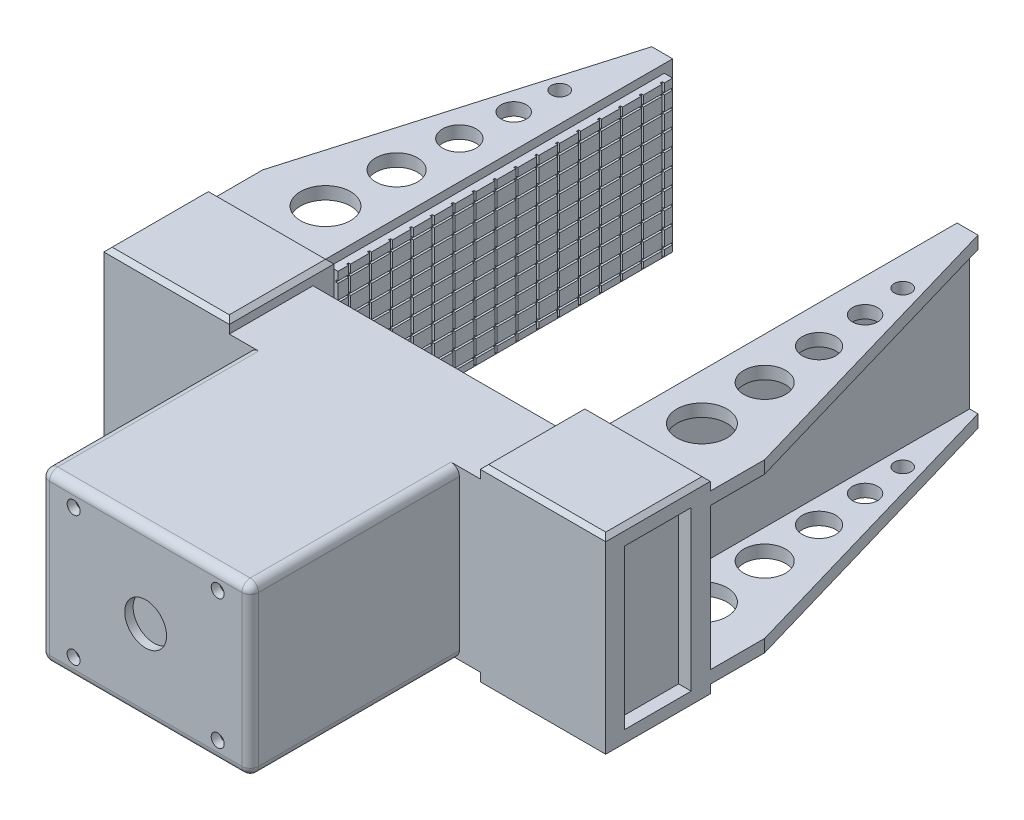
SolidWorks part; units mm, degrees
material "PLA+"
ref_plane "Front Plane" through (0, 0, 0) normal (0, 0, 1) x (1, 0, 0)
ref_plane "Top Plane" through (0, 0, 0) normal (0, 1, 0) x (1, 0, 0)
ref_plane "Right Plane" through (0, 0, 0) normal (1, 0, 0) x (0, 0, -1)
sketch "Sketch1" plane through (0, 0, 0) normal (0, 0, 1) x (1, 0, 0)
  line L1 (-17.2222, -15.5) -> (17.2222, -15.5) construction
  line L2 (-17.2222, -15.5) -> (-17.2222, 15.5) construction
  line L3 (-17.2222, 15.5) -> (17.2222, 15.5) construction
  line L4 (17.2222, -15.5) -> (17.2222, 15.5) construction
  line L5 (-17.2222, -15.5) -> (17.2222, 15.5) construction
  line L6 (-17.2222, 15.5) -> (17.2222, -15.5) construction
  line L7 (-25, -20) -> (25, -20)
  line L8 (-25, -20) -> (-25, 20)
  line L9 (-25, 20) -> (25, 20)
  line L10 (25, -20) -> (25, 20)
  line L11 (-25, -20) -> (25, 20) construction
  line L12 (-25, 20) -> (25, -20) construction
  circle A0 centre (0, 0) radius 5
  circle A1 centre (-17.2222, 15.5) radius 1.55
  circle A2 centre (17.2222, -15.5) radius 1.55
  circle A3 centre (17.2222, 15.5) radius 1.55
  circle A4 centre (-17.2222, -15.5) radius 1.55
  dimension "D1" = 10
  dimension "D3" = 3.1
  dimension "D2" = 15.5
  dimension "D4" = 50
  dimension "D5" = 40
extrude "Boss-Extrude2" add sketch "Sketch1" against normal blind 50 contours L8 L7 L10 L9
sketch "Sketch2" plane through (0, 0, 0) normal (0, 0, 1) x (1, 0, 0)
  circle A5 centre (-17.2222, -15.5) radius 1.55 construction
  circle A6 centre (17.2222, -15.5) radius 1.55 construction
  circle A7 centre (0, 0) radius 5 construction
  circle A8 centre (17.2222, 15.5) radius 1.55 construction
  circle A9 centre (-17.2222, 15.5) radius 1.55 construction
  circle A10 centre (-17.2222, -15.5) radius 1.55
  circle A11 centre (17.2222, -15.5) radius 1.55
  circle A12 centre (0, 0) radius 5
  circle A13 centre (17.2222, 15.5) radius 1.55
  circle A14 centre (-17.2222, 15.5) radius 1.55
extrude "Cut-Extrude1" cut sketch "Sketch2" against normal blind 2
sketch "Sketch3" plane through (0, 0, -50) normal (0, 0, -1) x (-1, 0, 0)
  line L1 (-60, -20) -> (60, -20)
  line L2 (-60, -20) -> (-60, 20)
  line L3 (-60, 20) -> (60, 20)
  line L4 (60, -20) -> (60, 20)
  line L5 (-60, -20) -> (60, 20) construction
  line L6 (-60, 20) -> (60, -20) construction
  point P0 (0, 0)
  dimension "D1" = 120
  dimension "D2" = 40
extrude "Boss-Extrude3" add sketch "Sketch3" along normal blind 20
sketch "Sketch4" plane through (0, 0, -70) normal (0, 0, -1) x (-1, 0, 0)
  line L0 (-60, -20) -> (60, -20) construction
  line L1 (-60, 20) -> (-34, 20)
  line L2 (-60, 20) -> (-60, -20)
  line L3 (-60, -20) -> (-34, -20)
  line L4 (-34, 20) -> (-34, -20)
  dimension "D1" = 26
extrude "Boss-Extrude4" add sketch "Sketch4" along normal blind 90 separate body
shell "Shell1" thickness 3
sketch "Sketch5" plane through (0, 0, 0) normal (0, 1, 0) x (1, 0, 0)
  line L0 (39, 160) -> (60, 88)
  line L1 (60, 70) -> (34, 70) construction
  line L3 (39, 160) -> (34, 160) construction
  line L4 (34, 70) -> (34, 160) construction
  line L5 (39, 160) -> (39, 70) construction
  line L6 (60, 88) -> (60, 70) construction
  line L7 (60, 70) -> (34, 70) construction
  line L8 (34, 70) -> (34, 160) construction
  line L9 (34, 160) -> (39, 160) construction
  line L10 (39, 160) -> (60, 160)
  line L11 (60, 160) -> (60, 88)
  circle A0 centre (41, 140) radius 2
  circle A1 centre (42, 130) radius 3
  circle A2 centre (43, 118) radius 4
  circle A3 centre (45, 88) radius 6
  circle A4 centre (44, 104) radius 5
  dimension "D3" = 4
  dimension "D4" = 6
  dimension "D5" = 8
  dimension "D6" = 12
  dimension "D7" = 10
  dimension "D1" = 5
  dimension "D2" = 18
  dimension "D8" = 10
  dimension "D9" = 12
  dimension "D10" = 14
  dimension "D11" = 16
  dimension "D12" = 20
extrude "Cut-Extrude2" cut sketch "Sketch5" against normal through all both and the other way through all
mirror "Mirror3" about plane through (0, 0, 0) normal (1, 0, 0) of bodies 106
sketch "Sketch7" plane through (34, 0, 0) normal (-1, 0, 0) x (0, 0, 1)
  line L0 (-160, 20) -> (-70, 20) construction
  line L1 (-158, 18) -> (-78, 18)
  line L2 (-158, 18) -> (-158, -18)
  line L3 (-158, -18) -> (-78, -18)
  line L4 (-78, 18) -> (-78, -18)
  line L5 (-160, -20) -> (-160, 20) construction
  line L6 (-160, -20) -> (-70, -20) construction
  dimension "D1" = 2
  dimension "D2" = 2
  dimension "D3" = 80
  dimension "D4" = 2
extrude "Boss-Extrude6" add sketch "Sketch7" along normal blind 2 separate body
sketch "Sketch8" plane through (32, 0, 0) normal (-1, 0, 0) x (0, 0, 1)
  line L0 (-156, 22.9676) -> (-156, -23.6029)
  line L1 (-158, 18) -> (-158, -18) construction
  line L2 (-155.5, 22.9676) -> (-155.5, -23.6029)
  line L3 (-156, 22.9676) -> (-155.5, 22.9676)
  line L4 (-156, -23.6029) -> (-155.5, -23.6029)
  dimension "D1" = 2
  dimension "D2" = 0.5
extrude "Cut-Extrude3" cut sketch "Sketch8" against normal blind 0.5
pattern_linear "LPattern1" count 16 spacing 5 along (0, 0, 1) of "Cut-Extrude3"
sketch "Sketch9" plane through (32, 0, 0) normal (-1, 0, 0) x (0, 0, 1)
  line L0 (-164.1465, 16) -> (-74.0827, 16)
  line L1 (-74.0827, 16) -> (-74.0827, 15.5)
  line L2 (-74.0827, 15.5) -> (-164.1465, 15.5)
  line L3 (-164.1465, 15.5) -> (-164.1465, 16)
  line L4 (-151, 18) -> (-155.5, 18) construction
  dimension "D1" = 0.5
  dimension "D2" = 2
extrude "Cut-Extrude4" cut sketch "Sketch9" against normal blind 0.5
pattern_linear "LPattern2" count 9 spacing 4 along (0, -1, 0) of "Cut-Extrude4"
mirror "Mirror4" about plane through (0, 0, 0) normal (1, 0, 0) of bodies 113
sketch "Sketch10" plane through (60, 0, 0) normal (1, 0, 0) x (0, 0, -1)
  line L0 (70, 20) -> (70, -20) construction
  line L1 (50, 23) -> (75, 23)
  line L2 (50, 23) -> (50, -23)
  line L3 (50, -23) -> (75, -23)
  line L4 (75, 23) -> (75, -23)
  line L5 (70, 20) -> (50, 20) construction
  line L6 (70, -20) -> (50, -20) construction
  point P10 (62.5, -23)
  dimension "D1" = 5
  dimension "D2" = 3
  dimension "D3" = 3
extrude "Boss-Extrude7" add sketch "Sketch10" against normal blind 30
sketch "Sketch11" plane through (60, 0, 0) normal (1, 0, 0) x (0, 0, -1)
  line L1 (54.4268, -19.1464) -> (70.4268, -19.1464)
  line L2 (54.4268, -19.1464) -> (54.4268, 18.8536)
  line L3 (54.4268, 18.8536) -> (70.4268, 18.8536)
  line L4 (70.4268, -19.1464) -> (70.4268, 18.8536)
  line L5 (54.4268, -19.1464) -> (70.4268, 18.8536) construction
  line L6 (54.4268, 18.8536) -> (70.4268, -19.1464) construction
  point P0 (62.4268, -0.1464)
  dimension "D1" = 16
  dimension "D2" = 38
extrude "Cut-Extrude5" cut sketch "Sketch11" against normal blind 3
sketch "Sketch12" plane through (-60, 0, 0) normal (-1, 0, 0) x (0, 0, 1)
  line L0 (-50, -20) -> (-50, -23) construction
  line L1 (-75, 23) -> (-50, 23)
  line L2 (-75, 23) -> (-75, -23)
  line L3 (-75, -23) -> (-50, -23)
  line L4 (-50, 23) -> (-50, -23)
extrude "Boss-Extrude8" add sketch "Sketch12" against normal blind 30
mirror "Mirror11" about plane through (0, 0, 0) normal (1, 0, 0) of "Cut-Extrude5"
chamfer "Chamfer1" distance 1 angle 45 16 edges at (-45, 23, -75) (-30, 23, -62.5) (-45, 23, -50) (-60, 23, -62.5) (-60, -23, -62.5) (-30, -23, -62.5) (-45, -23, -50) (-45, -23, -75) (45, -23, -50) (30, -23, -62.5) (45, -23, -75) (60, -23, -62.5) (45, 23, -50) (60, 23, -62.5) (30, 23, -62.5) (45, 23, -75)
fillet "Fillet1" radius 2 8 edges at (0, 20, 0) (25, 0, 0) (-25, 0, 0) (0, -20, 0) (-25, -20, -25) (25, -20, -25) (25, 20, -25) (-25, 20, -25)
